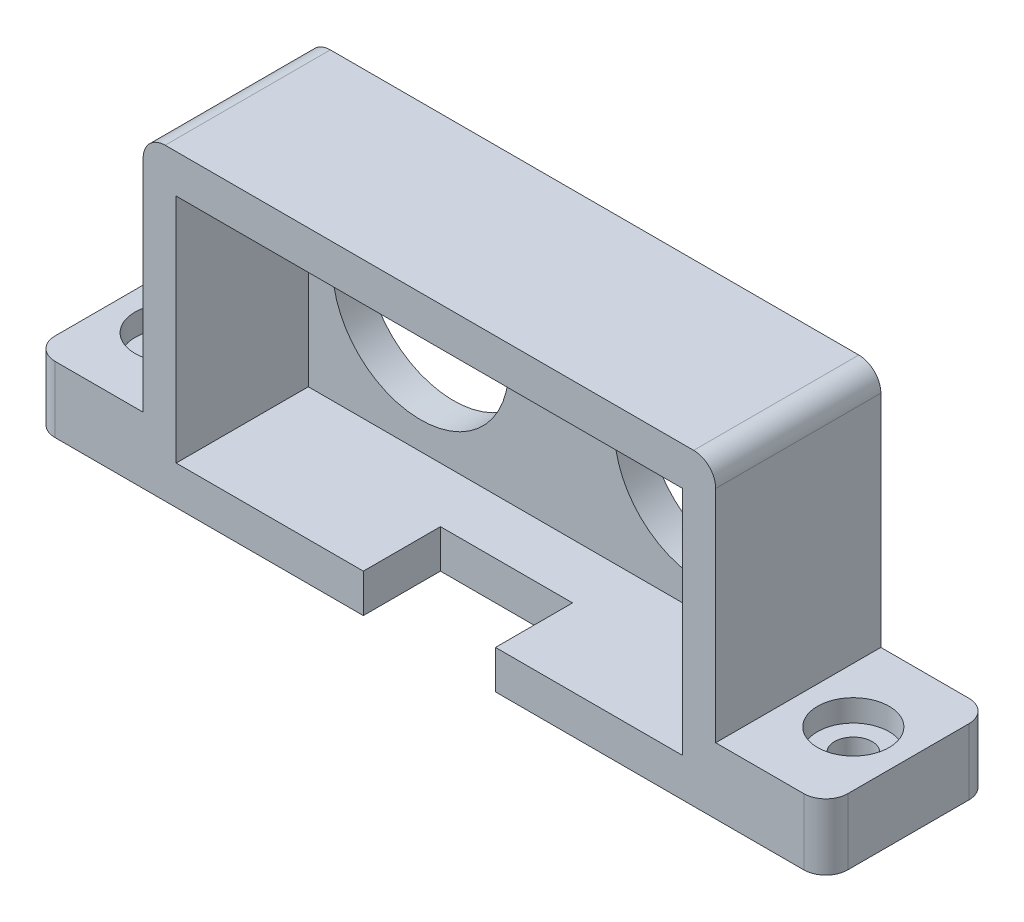
SolidWorks part; units mm, degrees
ref_plane "Plan de face" through (0, 0, 0) normal (0, 0, 1) x (1, 0, 0)
ref_plane "Plan de dessus" through (0, 0, 0) normal (0, 1, 0) x (1, 0, 0)
ref_plane "Plan de droite" through (0, 0, 0) normal (1, 0, 0) x (0, 0, -1)
sketch "Esquisse1" plane through (0, 0, 0) normal (0, 0, 1) x (1, 0, 0)
  line L0 (36, 0) -> (-36, 0)
  line L1 (-36, 0) -> (36, 0) construction
  line L2 (-36, 0) -> (-36, 28) construction
  line L3 (-36, 28) -> (36, 28) construction
  line L4 (36, 0) -> (36, 28) construction
  line L5 (-36, 0) -> (-36, 6)
  line L6 (-36, 6) -> (-26, 6)
  line L7 (-26, 6) -> (-26, 28)
  line L8 (-26, 28) -> (26, 28)
  line L9 (26, 28) -> (26, 6)
  line L10 (26, 6) -> (36, 6)
  line L11 (36, 6) -> (36, 0)
  point P4 (0, 0)
  dimension "D1" = 72
  dimension "D2" = 28
  dimension "D3" = 10
  dimension "D4" = 6
  dimension "D5" = 6
  dimension "D6" = 10
extrude "Boss.-Extru.1" add sketch "Esquisse1" along normal blind 15
sketch "Esquisse2" plane through (0, 0, 15) normal (0, 0, 1) x (1, 0, 0)
  line L0 (0, 0) -> (0, 28) construction
  line L1 (-23, 24.5) -> (23, 24.5) construction
  line L2 (-23, 24.5) -> (-23, 3.5) construction
  line L3 (-23, 3.5) -> (23, 3.5) construction
  line L4 (23, 24.5) -> (23, 3.5) construction
  line L5 (26, 28) -> (-26, 28) construction
  line L6 (-23, 14) -> (23, 14) construction
  line L9 (-23, 24.5) -> (23, 24.5)
  line L10 (-23, 24.5) -> (-23, 3.5)
  line L11 (-23, 3.5) -> (23, 3.5)
  line L12 (23, 24.5) -> (23, 3.5)
  point P4 (0, 3.5)
  point P9 (0, 14)
  dimension "D1" = 46
  dimension "D2" = 21
extrude "Enlèv. mat.-Extru.1" cut sketch "Esquisse2" against normal offset from surface (12 mm away) 3 up to face at (0, 10, 0)
sketch "Esquisse4" plane through (0, 0, 3) normal (0, 0, 1) x (1, 0, 0)
  line L0 (-4.8, 14) -> (4.8, 14) construction
  line L1 (0, 0) -> (0, 28) construction
  line L2 (-36, 0) -> (36, 0) construction
  line L3 (26, 28) -> (-26, 28) construction
  circle A0 centre (-12.8, 14) radius 8
  circle A1 centre (12.8, 14) radius 8
  point P12 (0, 14)
  point P13 (0, 14)
  dimension "D1" = 16
  dimension "D2" = 16
  dimension "D3" = 9.6
extrude "Enlèv. mat.-Extru.2" cut sketch "Esquisse4" against normal blind 3
sketch "Esquisse5" plane through (0, 0, 0) normal (0, -1, 0) x (1, 0, 0)
  line L0 (-36, 15) -> (36, 15) construction
  line L1 (-6, 15) -> (6, 15)
  line L2 (-6, 15) -> (-6, 8)
  line L3 (-6, 8) -> (6, 8)
  line L4 (6, 15) -> (6, 8)
  line L5 (0, 0) -> (0, 15) construction
  point P9 (0, 15)
  dimension "D1" = 12
  dimension "D2" = 7
extrude "Enlèv. mat.-Extru.3" cut sketch "Esquisse5" against normal up to surface (3.5 mm away) up to face at (0, 3.5, 9)
fillet "Congé1" radius 2 6 edges at (-36, 3, 0) (36, 3, 0) (36, 3, 15) (-36, 3, 15) (-26, 28, 7.5) (26, 28, 7.5)
sketch "Esquisse6" plane through (0, 6, 0) normal (0, 1, 0) x (1, 0, 0)
  line L0 (-36, -7.5) -> (36, -7.5) construction
  line L1 (-36, -13) -> (-36, -2) construction
  line L2 (36, -13) -> (36, -2) construction
  circle A0 centre (31, -7.5) radius 1
  circle A1 centre (-31, -7.5) radius 1
  dimension "D1" = 2
  dimension "D2" = 2
  dimension "D3" = 5
  dimension "D4" = 5
hole_wizard "Chambrage pour tête cylindrique fendue M31" positions "Esquisse7" profile "Esquisse9" counterbore size "M3" standard "ISO" end condition through all
sketch "Esquisse7" plane through (0, 6, 0) normal (0, 1, 0) x (1, 0, 0)
  point P0 (-31, -7.5)
  point P3 (31, -7.5)
sketch "Esquisse9" plane through (-31, 6, 7.5) normal (1, 0, 0) x (0, 0, 1)
  line L0 (0, 0) -> (0, 6)
  line L1 (0, 6) -> (1.7, 6)
  line L3 (1.7, 6) -> (1.7, 2)
  line L4 (1.7, 2) -> (3.25, 2)
  line L5 (3.25, 2) -> (3.25, 0)
  line L7 (3.25, 0) -> (0, 0)
  line L11 (0, -6.35) -> (0, 107.95) construction
  dimension "Diamètre du perçage jusqu'au prochain" = 3.4
  dimension "Profondeur du perçage jusqu'au prochain" = 6
  dimension "Diamètre du chambrage" = 6.5
  dimension "Profondeur du chambrage" = 2
